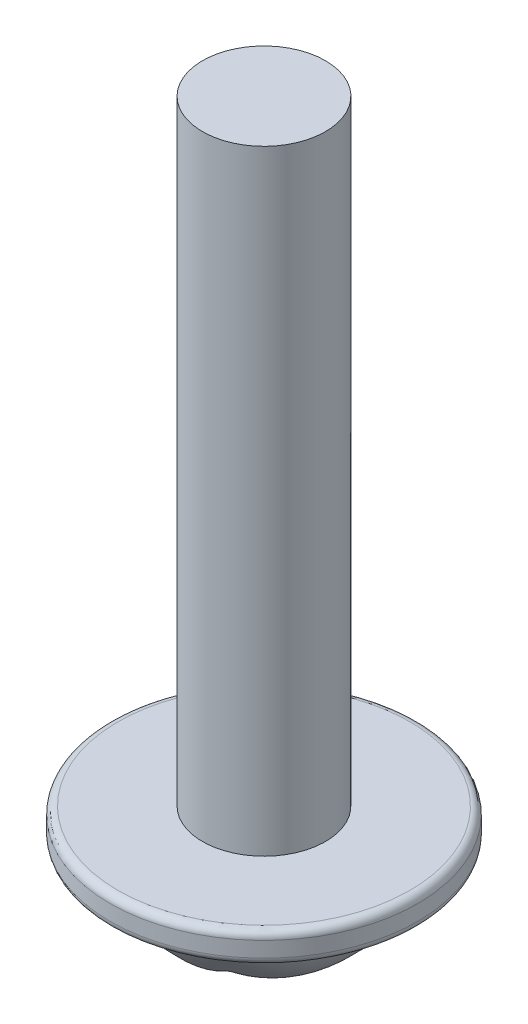
SolidWorks part; units mm, degrees
material "AISI 4140 Steel, quenched & tempered"
ref_plane "Front Plane" through (0, 0, 0) normal (1, 0, 0) x (0, 1, 0)
ref_plane "Top Plane" through (0, 0, 0) normal (0, 0, 1) x (0, 1, 0)
ref_plane "Right Plane" through (0, 0, 0) normal (0, 1, 0) x (-1, 0, 0)
sketch "Sketch1" plane through (0, 0, 0) normal (1, 0, 0) x (0, 1, 0)
  line L0 (-16.5151, 0) -> (46.9027, 0) construction
  line L1 (0, 11.8571) -> (0, -14.6667) construction
  line L2 (0, 4) -> (40, 4)
  line L3 (40, 4) -> (40, 0)
  line L4 (0, 10) -> (-2, 10)
  line L5 (-2, 10) -> (-2, 0)
  line L6 (-2, 0) -> (40, 0)
  line L7 (0, 10) -> (0, 4)
  line L8 (-10, 0) -> (-2, 0)
  arc A0 (-2, 7.746) -> (-8, 0) centre (0, 0) ccw
  dimension "D5" = 8
  dimension "D1" = 8
  dimension "D2" = 40
  dimension "D3" = 20
  dimension "D4" = 2
revolve "Revolve1" add sketch "Sketch1" angle 360 about L0 region at (0, 17.6667, 2.3333) region at (0, -4.4991, 3.1365)
sketch "Sketch2" plane through (0, -2, 0) normal (0, -1, 0) x (1, 0, 0)
  line L0 (-9.7647, 0.0339) -> (11.7784, -0.0339) construction
  line L1 (2.8868, -5) -> (5.7735, 0)
  line L2 (5.7735, 0) -> (2.8868, 5)
  line L3 (2.8868, 5) -> (-2.8868, 5)
  line L4 (-2.8868, 5) -> (-5.7735, 0)
  line L5 (-5.7735, 0) -> (-2.8868, -5)
  line L6 (-2.8868, -5) -> (2.8868, -5)
  circle A0 centre (0, 0) radius 5 construction
  circle A1 centre (0, 0) radius 10 construction
  dimension "D1" = 5
extrude "Cut-Extrude2" cut sketch "Sketch2" along normal blind 10 from offset 1
fillet "Fillet1" radius 0.25 18 edges at (0, -3, -5) (4.3301, -3, -2.5) (4.3301, -3, 2.5) (0, -3, 5) (-4.3301, -3, 2.5) (-4.3301, -3, -2.5) (-2.8868, -4.2689, -5) (-5.7735, -4.2689, 0) (-2.8868, -4.2689, 5) (2.8868, -4.2689, 5) (5.7735, -4.2689, 0) (2.8868, -4.2689, -5) (-4.3301, -6.245, -2.5) (0, -6.245, 5) (4.3301, -6.245, 2.5) (4.3301, -6.245, -2.5) (0, -6.245, -5) (-4.3301, -6.245, 2.5)
fillet "Fillet2" radius 0.5 2 edges at (0, 0, -10) (0, -2, -10)
